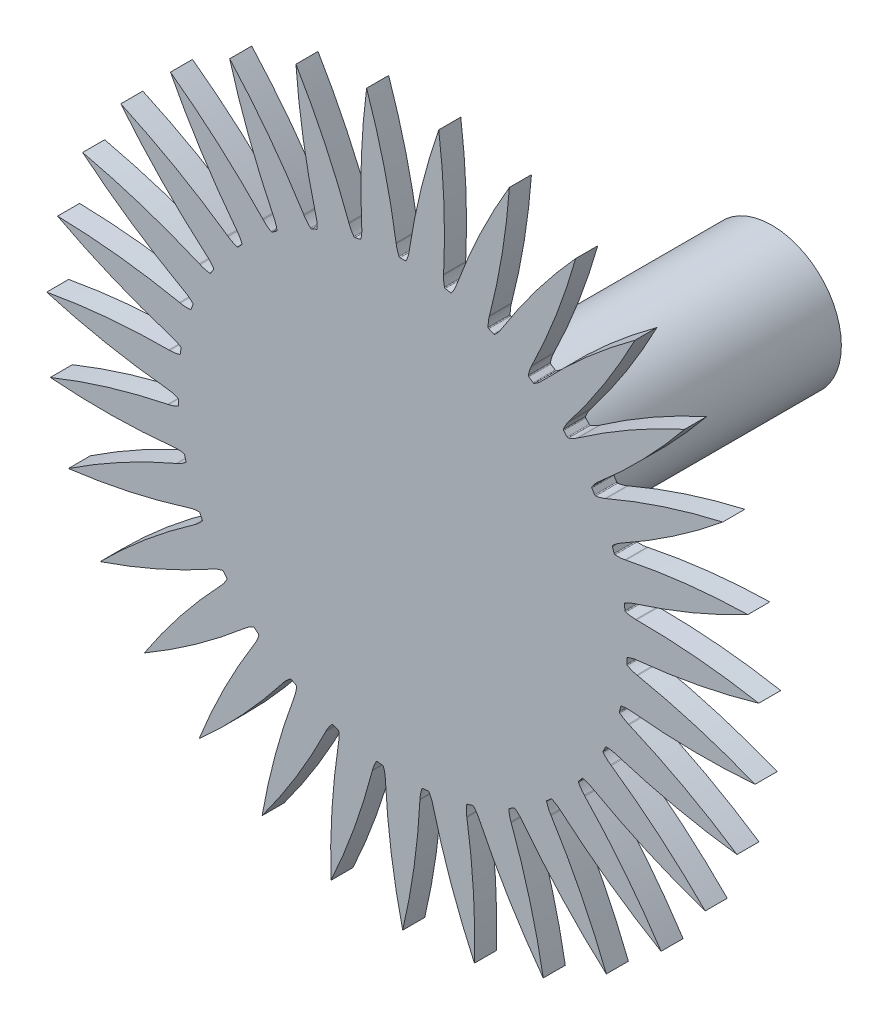
SolidWorks part; units mm, degrees
material "Pure Gold"
ref_plane "Front" through (0, 0, 0) normal (0, 0, 1) x (1, 0, 0)
ref_plane "Top" through (0, 0, 0) normal (0, 1, 0) x (1, 0, 0)
ref_plane "Right" through (0, 0, 0) normal (1, 0, 0) x (0, 0, -1)
sketch "Sketch1" plane through (0, 0, 0) normal (0, 0, 1) x (1, 0, 0)
  line L0 (0, 0) -> (0, 500) construction
  circle A1 centre (0, 0) radius 500
  dimension "D1" = 1000
extrude "Extrude1" add sketch "Sketch1" along normal blind 12.7
sketch "Sketch2" plane through (0, 0, 12.7) normal (0, 0, 1) x (1, 0, 0)
  line L0 (0, 0) -> (0, 500) construction
  line L1 (3.7322, 135.1942) -> (3.81, 135.7022)
  line L2 (-3.7322, 135.1942) -> (-3.81, 135.7022)
  circle A0 centre (0, 0) radius 500 construction
  arc A1 (1.905, 129.3522) -> (-1.905, 129.3522) centre (0, 0) ccw
  arc A2 (1.905, 129.3522) -> (3.7322, 135.1942) centre (-16.3537, 138.2697) ccw
  arc A3 (3.81, 135.7022) -> (241.2315, 437.9582) centre (390.2485, 76.5306) cw
  arc A4 (-3.81, 135.7022) -> (-241.2315, 437.9582) centre (-390.2485, 76.5306) ccw
  arc A5 (-1.905, 129.3522) -> (-3.7322, 135.1942) centre (16.3537, 138.2697) cw
  dimension "D1" = 7.62
  dimension "D2" = 20.32
  dimension "D4" = 6.35
  dimension "D5" = 3.81
  dimension "D6" = 129.3662
  dimension "D7" = 390.9425
  dimension "D3" = 0.508
extrude "Cut-Extrude1" cut sketch "Sketch2" against normal through all and the other way through all flip side to cut
fillet "Fillet1" radius 0.635 2 edges at (1.905, 129.3522, 6.35) (-1.905, 129.3522, 6.35)
pattern_circular "CirPattern1" count 31 over 360 about axis through (0, 0, 12.7) along (0, 0, -1) of "Cut-Extrude1", "Fillet1"
sketch "Sketch3" plane through (0, 0, 0) normal (0, 0, -1) x (-1, 0, 0)
  circle A0 centre (0, 0) radius 40
  dimension "D1" = 80
extrude "Extrude2" add sketch "Sketch3" along normal blind 200
equation "\"wheelSize\"= 100cm"
equation "\"D1@Sketch1\"=\"wheelSize\""
equation "\"D1@Sketch3\" = \"HoleMountDiameter@PrintingPress.Assembly\""
equation "\"D1@Extrude2\" = 2 * \"RivetLength@PrintingPress.Assembly\""
